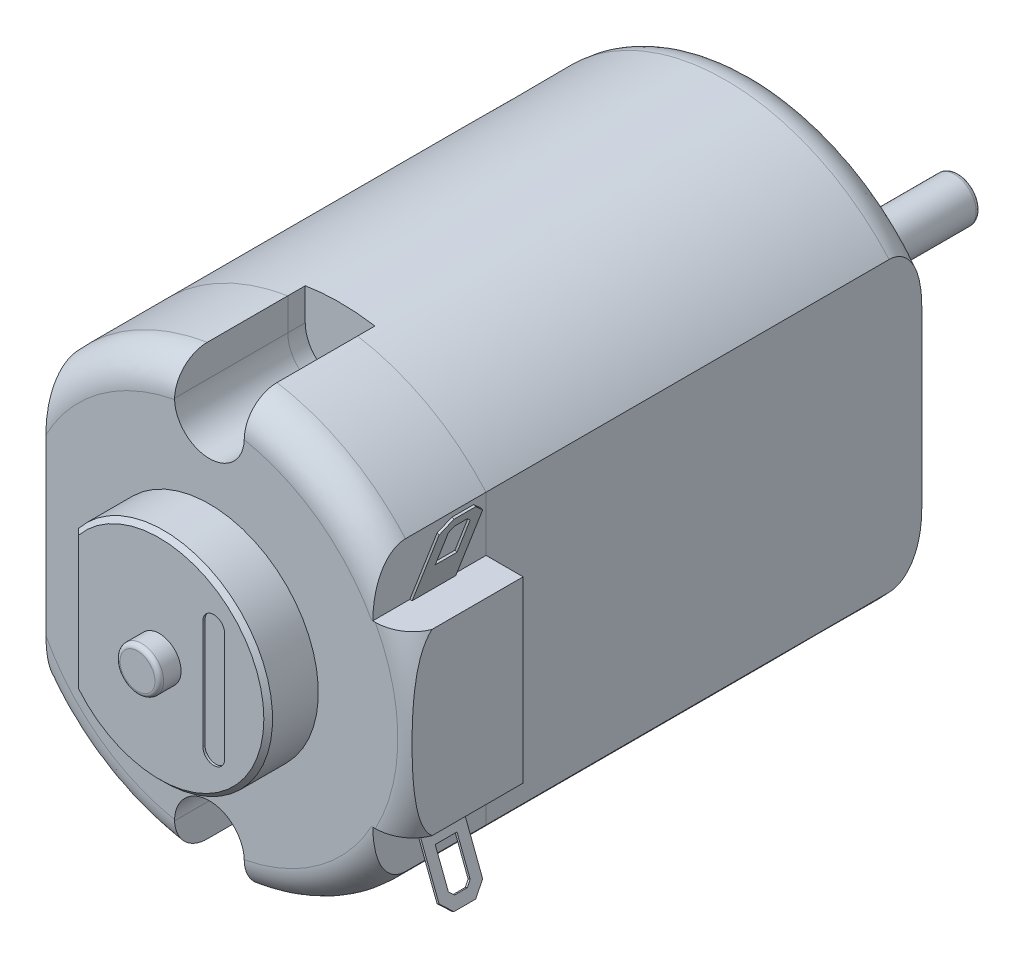
SolidWorks part; units mm, degrees
ref_plane "Front Plane" through (0, 0, 0) normal (0, 0, 1) x (1, 0, 0)
ref_plane "Top Plane" through (0, 0, 0) normal (0, 1, 0) x (1, 0, 0)
ref_plane "Right Plane" through (0, 0, 0) normal (1, 0, 0) x (0, 0, -1)
sketch "Sketch1" plane through (0, 0, 0) normal (0, 0, 1) x (1, 0, 0)
  line L1 (7.5, -6.6144) -> (-7.5, -6.6144)
  line L2 (7.5, -6.6144) -> (7.5, 6.6144)
  line L3 (7.5, 6.6144) -> (-7.5, 6.6144)
  line L4 (-7.5, -6.6144) -> (-7.5, 6.6144)
  line L5 (7.5, -6.6144) -> (-7.5, 6.6144) construction
  line L6 (7.5, 6.6144) -> (-7.5, -6.6144) construction
  ellipse E0 centre (0, 0) end of major axis (0, 10) minor radius 10
  dimension "D1" = 15
  dimension "D2" = 20
  dimension "D3" = 20
extrude "Boss-Extrude1" add sketch "Sketch1" along normal mid plane 20 contours L4 L1 L2 L3 | L3 E0 | L1 E0 region at (0, -7.9904, 0) region at (0, 0, 0) region at (0, 7.9904, 0)
sketch "Sketch2" plane through (0, 0, -10) normal (0, 0, -1) x (-1, 0, 0)
  circle A0 centre (0, 0) radius 3
  circle A1 centre (0, 0) radius 2.8
  dimension "D1" = 6
  dimension "D2" = 0.2
extrude "Boss-Extrude2" add sketch "Sketch2" along normal blind 1.1
sketch "Sketch3" plane through (0, 0, -10) normal (0, 0, -1) x (-1, 0, 0)
  circle A0 centre (0, 0) radius 2.8
  circle A1 centre (0, 0) radius 2.8 construction
extrude "Boss-Extrude3" add sketch "Sketch3" along normal offset from surface (0.7 mm away) 0.4 up to face at (-3, 0, -11.1)
sketch "Sketch4" plane through (0, 0, -10.7) normal (0, 0, -1) x (-1, 0, 0)
  circle A0 centre (0, 0) radius 1
  dimension "D1" = 2
extrude "Boss-Extrude4" add sketch "Sketch4" along normal blind 8.5
sketch "Sketch5" plane through (0, 0, -10) normal (0, 0, -1) x (-1, 0, 0)
  line L0 (3, 0) -> (7.5, 0) construction
  line L1 (7.5, -6.6144) -> (7.5, 6.6144) construction
  circle A0 centre (0, 0) radius 3 construction
  circle A1 centre (5.25, 0) radius 0.7
  dimension "D1" = 1.4
extrude "Cut-Extrude1" cut sketch "Sketch5" against normal blind 0.1
sketch "Sketch6" plane through (0, 0, 10) normal (0, 0, 1) x (1, 0, 0)
  point P0 (0, 0)
  line M1 (-7.5, 6.6144) -> (-7.5, -6.6144)
  ellipse M2 centre (0, 0) end of major axis (-10, 0) minor radius 10 (-7.5, -6.6144) -> (7.5, -6.6144) ccw
  line M3 (7.5, -6.6144) -> (7.5, 6.6144)
  ellipse M4 centre (0, 0) end of major axis (-10, 0) minor radius 10 (7.5, 6.6144) -> (-7.5, 6.6144) ccw
extrude "Boss-Extrude5" add sketch "Sketch6" along normal blind 5.2 separate body contours M4 M1 M2 M3 region at (0, 0, 10)
sketch "Sketch7" plane through (0, 0, 15.2) normal (0, 0, 1) x (1, 0, 0)
  line L0 (-3.9, 3.1289) -> (-3.9, -3.1289)
  circle A0 centre (0, 0) radius 5
  point P5 (5, 0)
  dimension "D1" = 10
  dimension "D2" = 8.9
extrude "Boss-Extrude6" add sketch "Sketch7" along normal blind 2.3 contours L0 A0 region at (0.2766, 0, 15.2)
sketch "Sketch8" plane through (0, 0, 17.5) normal (0, 0, 1) x (1, 0, 0)
  circle A0 centre (0, 0) radius 1
  dimension "D1" = 2
extrude "Boss-Extrude7" add sketch "Sketch8" along normal blind 1
sketch "Sketch9" plane through (0, 0, 17.5) normal (0, 0, 1) x (1, 0, 0)
  line L0 (2.5, -2.5) -> (2.5, 2.5) construction
  line L1 (2, -2.5) -> (2, 2.5)
  line L2 (3, -2.5) -> (3, 2.5)
  arc A0 (2, -2.5) -> (3, -2.5) centre (2.5, -2.5) ccw
  arc A1 (3, 2.5) -> (2, 2.5) centre (2.5, 2.5) ccw
  point P2 (2.5, 0)
  point P8 (2.5, 3)
  point P11 (2.5, -3)
  point P15 (0, 0)
  dimension "D2" = 6
  dimension "D3" = 1
  dimension "D4" = 2.5
extrude "Cut-Extrude2" cut sketch "Sketch9" against normal blind 0.1
sketch "Sketch10" plane through (0, 0, 15.2) normal (0, 0, 1) x (1, 0, 0)
  line L0 (-1.6, -9.8712) -> (1.6, -9.8712)
  line L1 (-1.6, -9.8712) -> (-1.6, -8.4)
  line L2 (1.6, -9.8712) -> (1.6, -8.4)
  line L3 (-1.6, -8.4) -> (1.6, -8.4)
  line L4 (-1.6, 9.8712) -> (1.6, 9.8712)
  line L5 (-1.6, 9.8712) -> (-1.6, 8.4)
  line L6 (1.6, 9.8712) -> (1.6, 8.4)
  line L7 (-1.6, 8.4) -> (1.6, 8.4)
  circle A0 centre (0, -8.4) radius 1.6
  circle A1 centre (0, 8.4) radius 1.6
  ellipse E0 centre (0, 0) end of major axis (-10, 0) minor radius 10 (-7.5, -6.6144) -> (7.5, -6.6144) ccw construction
  ellipse E1 centre (0, 0) end of major axis (-10, 0) minor radius 10 (7.5, 6.6144) -> (-7.5, 6.6144) ccw construction
  ellipse M6 centre (0, 0) end of major axis (-10, 0) minor radius 10 (7.5, 6.6144) -> (-7.5, 6.6144) ccw
  ellipse M8 centre (0, 0) end of major axis (-10, 0) minor radius 10 (-7.5, -6.6144) -> (7.5, -6.6144) ccw
  dimension "D1" = 3.2
extrude "Cut-Extrude3" cut sketch "Sketch10" against normal blind 6 contours L3 A0 | L3 A0 L0 | A0 L1 L0 | A0 L0 M8 | L0 A0 | A0 L0 M8 | A0 L0 L2 | L7 A1 | L7 A1 L4 | A1 L4 L5 | A1 L6 L4 | A1 L4 M6 | L4 A1 | A1 L4 M6 region at (-1.3343, -9.5292, 15.2) region at (-0.8386, -9.9226, 15.2) region at (0, -9.0556, 15.2) region at (0, -9.9229, 15.2) region at (0, -7.7209, 15.2) region at (0.8386, -9.9226, 15.2) region at (1.3343, -9.5292, 15.2) region at (-0.8386, 9.9226, 15.2) region at (-1.3343, 9.5292, 15.2) region at (0, 9.9229, 15.2) region at (0, 9.0556, 15.2) region at (0, 7.7209, 15.2) region at (0.8386, 9.9226, 15.2) region at (1.3343, 9.5292, 15.2)
sketch "Sketch11" plane through (0, 0, 15.2) normal (0, 0, 1) x (1, 0, 0)
  line L0 (7.5, 4.1) -> (7.5, -4.1)
  line L1 (7.5, 4.1) -> (9.2, 4.1)
  line L2 (7.5, -4.1) -> (9.2, -4.1)
  line L3 (9.2, 4.1) -> (9.2, -4.1)
  line L4 (7.5, -6.6144) -> (7.5, 6.6144) construction
  arc A0 (-3.9, -3.1289) -> (-3.9, 3.1289) centre (0, 0) ccw construction
  point P6 (7.5, 0)
  point P10 (5, 0)
  dimension "D1" = 1.7
  dimension "D2" = 8.2
extrude "Boss-Extrude8" add sketch "Sketch11" against normal up to vertex (5.2 mm away) up to point (7.5, -6.6144, 10)
fillet "Fillet1" radius 0.2 1 edges at (1, 0, 18.5)
fillet "Fillet2" radius 0.2 1 edges at (-1, 0, -19.2)
fillet "Fillet3" radius 1.5 2 edges at (0, -10, -10) (0, 10, -10)
fillet "Fillet4" radius 1.5 4 edges at (4.8326, -8.7548, 15.2) (-4.8326, -8.7548, 15.2) (4.8326, 8.7548, 15.2) (-4.8326, 8.7548, 15.2)
chamfer "Chamfer1" distance 0.2 angle 45 2 edges at (-3.9, 0, 17.5) (5, 0, 17.5)
ref_axis "Axis1" through (0, 0, 23.6796) along (0, 0, -1)
sketch "Sketch13" plane through (0, 0, 0) normal (0, -1, 0) x (0, 0, -1)
  line L2 (0, -8.65) -> (0, 8.65) construction
  line L3 (-15.2, 1.5992) -> (-15.2, -1.5992) construction
  line L8 (-15.2, 8.65) -> (-15.2, 10.15)
  line L9 (-15.2, 10.15) -> (-13.7, 10.15)
  arc A1 (-13.7, 10.15) -> (-15.2, 8.65) centre (-13.7, 8.65) ccw
  point P23 (0, 0)
  dimension "D1" = 17.3
  dimension "D3" = 1.5
revolve "Cut-Revolve1" cut sketch "Sketch13" angle 29 about axis through (0, 0, 23.6796) along (0, 0, -1) other way angle 29 reverse direction yes
sketch "Sketch14" plane through (0, 0, 10) normal (0, 0, -1) x (-1, 0, 0)
  line L0 (-7.5, 4.1) -> (-7.5934, 4.0643)
  line L1 (-7.5, 4.1) -> (-8.9298, 7.8357)
  line L2 (-7.5934, 4.0643) -> (-9.0232, 7.8)
  line L3 (-8.9298, 7.8357) -> (-9.0232, 7.8)
  line L4 (-7.5, -4.1) -> (-7.5934, -4.0643) construction
  line L5 (-7.5, -4.1) -> (-8.9298, -7.8357) construction
  line L6 (-7.5934, -4.0643) -> (-9.0232, -7.8) construction
  line L7 (-8.9298, -7.8357) -> (-9.0232, -7.8) construction
  dimension "D1" = 0.1
  dimension "D2" = 4
  dimension "D3" = 15.6
extrude "Boss-Extrude9" add sketch "Sketch14" against normal blind 2 from offset 1.5 offset against normal yes
sketch "Sketch15" plane through (5.2665, -2.0156, 0) normal (0.9339, -0.3574, 0) x (0, 0, -1)
  line L0 (-13.5, 10.5099) -> (-11.5, 10.5099) construction
  line L1 (-13, 10.0099) -> (-12, 10.0099)
  line L2 (-13, 10.0099) -> (-13, 8.1099)
  line L3 (-13, 8.1099) -> (-12, 8.1099)
  line L4 (-12, 10.0099) -> (-12, 8.1099)
  line L5 (-13, 9.8028) -> (-12.7929, 10.0099)
  line L6 (-12, 10.0099) -> (-11.5, 10.0099) construction
  line L7 (-12, 10.0099) -> (-12, 10.5099) construction
  line L8 (-12, 10.5099) -> (-11.5, 10.5099) construction
  line L9 (-11.5, 10.0099) -> (-11.5, 10.5099) construction
  line L10 (-13, 10.5099) -> (-13.5, 10.0099)
  line L11 (-13.5, 10.5099) -> (-13.5, 6.5482) construction
  line L12 (-12, 10.5099) -> (-11.5, 10.0099)
  line L13 (-12.2071, 10.0099) -> (-12, 9.8028)
  line L14 (-13, 10.5099) -> (-13.5, 10.5099)
  line L15 (-13.5, 10.5099) -> (-13.5, 10.0099)
  line L16 (-12, 10.5099) -> (-11.5, 10.5099)
  line L17 (-11.5, 10.5099) -> (-11.5, 10.0099)
  point P6 (-12.5, 10.5099)
  point P7 (-12.5, 10.0099)
  line M9 (-13.5, 10.5099) -> (-13.5, 6.5482)
  line M11 (-11.5, 6.5482) -> (-11.5, 10.5099)
  line M12 (-11.5, 10.5099) -> (-13.5, 10.5099)
  dimension "D1" = 0.5
  dimension "D2" = 1.9
  dimension "D3" = 0.5
  dimension "D4" = 1
extrude "Cut-Extrude4" cut sketch "Sketch15" against normal up to surface (0.1 mm away) contours L13 L1 L5 L2 L3 L4 | L10 M12 M9 | L12 M12 M11 region at (8.4976, 6.4268, 12.5) region at (8.9636, 7.6443, 13.3333) region at (8.9636, 7.6443, 11.6667) up to face at (8.2149, 5.9679, 12.5)
mirror "Mirror1" about plane through (0, 0, 0) normal (0, 1, 0) of "Cut-Extrude4", "Boss-Extrude9"
